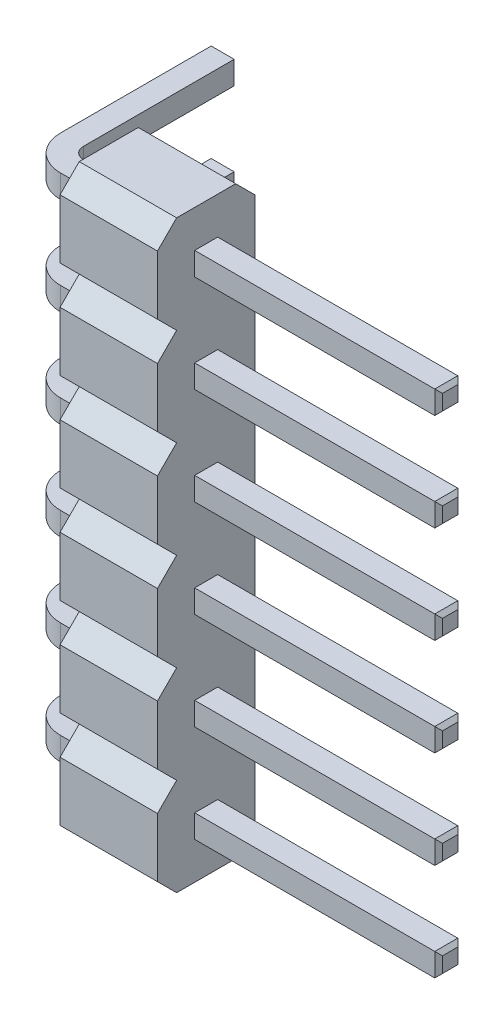
SolidWorks part; units mm, degrees
ref_plane "Front Plane" through (0, 0, 0) normal (0, 0, 1) x (1, 0, 0)
ref_plane "Top Plane" through (0, 0, 0) normal (0, 1, 0) x (1, 0, 0)
ref_plane "Right Plane" through (0, 0, 0) normal (1, 0, 0) x (0, 0, -1)
sketch "Sketch1" plane through (0, 0, 0) normal (1, 0, 0) x (0, 0, -1)
  line L0 (0, 0) -> (-1.27, 0) construction
  line L5 (-1.27, 0) -> (-1.27, 1.27) construction
  line L6 (-2.04, 1.27) -> (-0.5, 1.27)
  line L7 (-0.5, 1.27) -> (0, 0.77)
  line L8 (0, 0.77) -> (0, -0.77)
  line L9 (-2.54, 0.77) -> (-2.54, -0.77)
  line L10 (-2.04, 1.27) -> (-2.54, 0.77)
  line L11 (-0.5, -1.27) -> (0, -0.77)
  line L12 (-2.04, -1.27) -> (-0.5, -1.27)
  line L13 (-2.04, -1.27) -> (-2.54, -0.77)
  point P13 (-2.54, 0)
  dimension "D1" = 1.27
  dimension "D2" = 45
  dimension "D3" = 0.5
extrude "Plastic" add sketch "Sketch1" along normal blind 2.54
sketch "Sketch2" plane through (0, 0, 0) normal (0, 1, 0) x (1, 0, 0)
  line L0 (-1.56, 3.36) -> (-1.56, -0.67) construction
  line L1 (-0.96, -1.27) -> (8.9, -1.27) construction
  line L2 (0, -2.04) -> (0, -0.5) construction
  line L3 (-1.86, 3.36) -> (-1.86, -0.67)
  line L4 (-0.96, -1.57) -> (8.9, -1.57)
  line L5 (-1.26, 3.36) -> (-1.26, -0.67)
  line L6 (-0.96, -0.97) -> (8.9, -0.97)
  line L7 (-1.86, 3.36) -> (-1.26, 3.36)
  line L8 (8.9, -1.57) -> (8.9, -0.97)
  line L9 (2.54, -2.54) -> (0, -2.54) construction
  line L10 (2.54, -2.04) -> (2.54, -0.5) construction
  arc A0 (-1.56, -0.67) -> (-0.96, -1.27) centre (-0.96, -0.67) ccw construction
  arc A1 (-1.86, -0.67) -> (-0.96, -1.57) centre (-0.96, -0.67) ccw
  arc A2 (-1.26, -0.67) -> (-0.96, -0.97) centre (-0.96, -0.67) ccw
  point P5 (0, -1.27)
  dimension "D1" = 0.6
  dimension "D4" = 8.9
  dimension "D5" = 5.9
  dimension "D6" = 4.4
  dimension "D2" = 0.3
  dimension "D3" = 0.3
extrude "Contact" add sketch "Sketch2" along normal mid plane 0.6
chamfer "Chamfer1" distance 0.1 angle 45 8 edges at (8.9, 0.3, 1.27) (8.9, 0, 1.57) (8.9, -0.3, 1.27) (8.9, 0, 0.97) (-1.56, 0.3, -3.36) (-1.26, 0, -3.36) (-1.86, 0, -3.36) (-1.56, -0.3, -3.36)
pattern_linear "LPattern1" count 6 spacing 2.54 along (0, 1, 0) of "Plastic", "Contact", "Chamfer1"
sketch "Sketch3" plane through (0, 0, -3.36) normal (0, 0, -1) x (-1, 0, 0)
  line L0 (1.36, 0) -> (1.56, 0) construction
  line L1 (1.36, 0.2) -> (1.36, -0.2) construction
  line L2 (1.56, 0) -> (1.56, -0.2) construction
  line L3 (1.36, -0.2) -> (1.76, -0.2) construction
ref_axis "Axis1" through (-1.56, 0, -3.36) along (0, 0, 1)
